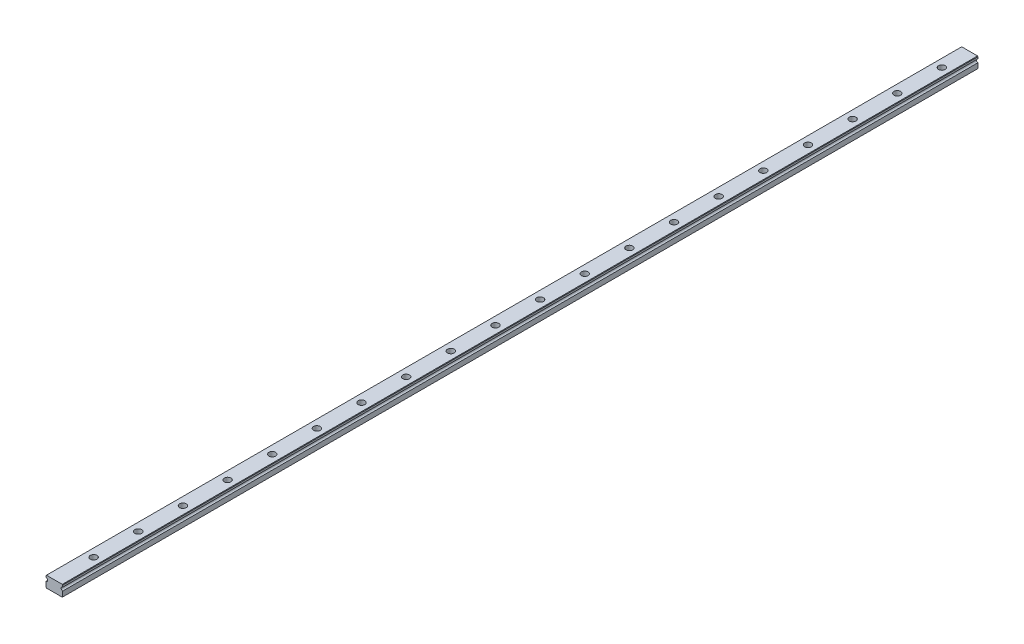
SolidWorks part; units mm, degrees
ref_plane "前视基准面" through (0, 0, 0) normal (0, 0, 1) x (1, 0, 0)
ref_plane "上视基准面" through (0, 0, 0) normal (0, 1, 0) x (1, 0, 0)
ref_plane "右视基准面" through (0, 0, 0) normal (1, 0, 0) x (0, 0, -1)
other "Configuration Table"
sketch "草图1" plane through (0, 0, 0) normal (0, 0, 1) x (1, 0, 0)
  line L0 (-7.6432, 0.2342) -> (-7.6432, -4.3658)
  line L1 (-7.6432, -4.3658) -> (-7.2432, -4.7658)
  line L2 (-7.2432, -4.7658) -> (6.9568, -4.7658)
  line L3 (6.9568, -4.7658) -> (7.3568, -4.3658)
  line L4 (7.3568, -4.3658) -> (7.3568, 0.2342)
  line L5 (7.3568, 3.2342) -> (7.3568, 4.8342)
  line L6 (7.3568, 4.8342) -> (6.9568, 5.2342)
  line L7 (6.9568, 5.2342) -> (-7.2432, 5.2342)
  line L8 (-7.2432, 5.2342) -> (-7.6432, 4.8342)
  line L9 (-7.6432, 4.8342) -> (-7.6432, 3.2342)
  arc A0 (5.8568, 1.7342) -> (7.3568, 0.2342) centre (7.3568, 1.7342) ccw
  arc A1 (7.3568, 3.2342) -> (5.8568, 1.7342) centre (7.3568, 1.7342) ccw
  arc A2 (-7.6432, 0.2342) -> (-7.6432, 3.2342) centre (-7.6432, 1.7342) ccw
extrude "凸台-拉伸1" add sketch "草图1" along normal blind 1000
sketch "草图2" plane through (0, 5.2342, 0) normal (0, 1, 0) x (1, 0, 0)
  circle A0 centre (0, -4.969) radius 1.5
  dimension "D1" = 3
extrude "切除-拉伸1" cut sketch "草图2" against normal blind 20
sketch "草图3" plane through (0, 5.2342, 0) normal (0, 1, 0) x (1, 0, 0)
  circle A0 centre (0, -4.969) radius 3
  dimension "D1" = 6
extrude "切除-拉伸2" cut sketch "草图3" against normal blind 4.5
sketch "草图4" plane through (0, 5.2342, 0) normal (0, 1, 0) x (1, 0, 0)
  line L0 (0, 0) -> (0, -1341.5051) construction
pattern_linear "阵列(线性)1" count 25 spacing 40 along (0, 0, 1) of "切除-拉伸2", "切除-拉伸1"
sketch "草图5" plane through (0, 0, 1000) normal (0, 0, 1) x (1, 0, 0)
  line L10 (-7.6432, 0.2342) -> (-7.6432, -4.3658)
  line L11 (-7.6432, -4.3658) -> (-7.2432, -4.7658)
  line L12 (-7.2432, -4.7658) -> (6.9568, -4.7658)
  line L13 (6.9568, -4.7658) -> (7.3568, -4.3658)
  line L14 (7.3568, -4.3658) -> (7.3568, 0.2342)
  line L15 (7.3568, 3.2342) -> (7.3568, 4.8342)
  line L16 (7.3568, 4.8342) -> (6.9568, 5.2342)
  line L17 (6.9568, 5.2342) -> (-7.2432, 5.2342)
  line L18 (-7.2432, 5.2342) -> (-7.6432, 4.8342)
  line L19 (-7.6432, 4.8342) -> (-7.6432, 3.2342)
  line L20 (-7.6432, 0.2342) -> (-7.6432, -4.3658)
  line L21 (-7.6432, -4.3658) -> (-7.2432, -4.7658)
  line L22 (-7.2432, -4.7658) -> (6.9568, -4.7658)
  line L23 (6.9568, -4.7658) -> (7.3568, -4.3658)
  line L24 (7.3568, -4.3658) -> (7.3568, 0.2342)
  line L25 (7.3568, 3.2342) -> (7.3568, 4.8342)
  line L26 (7.3568, 4.8342) -> (6.9568, 5.2342)
  line L27 (6.9568, 5.2342) -> (-7.2432, 5.2342)
  line L28 (-7.2432, 5.2342) -> (-7.6432, 4.8342)
  line L29 (-7.6432, 4.8342) -> (-7.6432, 3.2342)
  arc A2 (-7.6432, 0.2342) -> (-7.6432, 3.2342) centre (-7.6432, 1.7342) ccw
  arc A3 (7.3568, 3.2342) -> (7.3568, 0.2342) centre (7.3568, 1.7342) ccw
  arc A4 (-7.6432, 0.2342) -> (-7.6432, 3.2342) centre (-7.6432, 1.7342) ccw
  arc A5 (7.3568, 3.2342) -> (7.3568, 0.2342) centre (7.3568, 1.7342) ccw
  dimension "D1" = 0
sketch "草图6" plane through (0, 0, 0) normal (0, 0, -1) x (-1, 0, 0)
  line L10 (7.6432, 3.2342) -> (7.6432, 4.8342)
  line L11 (7.6432, 4.8342) -> (7.2432, 5.2342)
  line L12 (7.2432, 5.2342) -> (-6.9568, 5.2342)
  line L13 (-6.9568, 5.2342) -> (-7.3568, 4.8342)
  line L14 (-7.3568, 4.8342) -> (-7.3568, 3.2342)
  line L15 (-7.3568, 0.2342) -> (-7.3568, -4.3658)
  line L16 (-7.3568, -4.3658) -> (-6.9568, -4.7658)
  line L17 (-6.9568, -4.7658) -> (7.2432, -4.7658)
  line L18 (7.2432, -4.7658) -> (7.6432, -4.3658)
  line L19 (7.6432, -4.3658) -> (7.6432, 0.2342)
  line L20 (7.6432, 3.2342) -> (7.6432, 4.8342)
  line L21 (7.6432, 4.8342) -> (7.2432, 5.2342)
  line L22 (7.2432, 5.2342) -> (-6.9568, 5.2342)
  line L23 (-6.9568, 5.2342) -> (-7.3568, 4.8342)
  line L24 (-7.3568, 4.8342) -> (-7.3568, 3.2342)
  line L25 (-7.3568, 0.2342) -> (-7.3568, -4.3658)
  line L26 (-7.3568, -4.3658) -> (-6.9568, -4.7658)
  line L27 (-6.9568, -4.7658) -> (7.2432, -4.7658)
  line L28 (7.2432, -4.7658) -> (7.6432, -4.3658)
  line L29 (7.6432, -4.3658) -> (7.6432, 0.2342)
  arc A2 (7.6432, 3.2342) -> (7.6432, 0.2342) centre (7.6432, 1.7342) ccw
  arc A3 (-7.3568, 0.2342) -> (-7.3568, 3.2342) centre (-7.3568, 1.7342) ccw
  arc A4 (7.6432, 3.2342) -> (7.6432, 0.2342) centre (7.6432, 1.7342) ccw
  arc A5 (-7.3568, 0.2342) -> (-7.3568, 3.2342) centre (-7.3568, 1.7342) ccw
  dimension "D1" = 0
extrude "切除-拉伸4" cut sketch "草图6" against normal blind 80
sketch "草图7" plane through (0, 0, 80) normal (0, 0, -1) x (-1, 0, 0)
  line L10 (7.6432, 3.2342) -> (7.6432, 4.8342)
  line L11 (7.6432, 4.8342) -> (7.2432, 5.2342)
  line L12 (7.2432, 5.2342) -> (-6.9568, 5.2342)
  line L13 (-6.9568, 5.2342) -> (-7.3568, 4.8342)
  line L14 (-7.3568, 4.8342) -> (-7.3568, 3.2342)
  line L15 (-7.3568, 0.2342) -> (-7.3568, -4.3658)
  line L16 (-7.3568, -4.3658) -> (-6.9568, -4.7658)
  line L17 (-6.9568, -4.7658) -> (7.2432, -4.7658)
  line L18 (7.2432, -4.7658) -> (7.6432, -4.3658)
  line L19 (7.6432, -4.3658) -> (7.6432, 0.2342)
  line L20 (7.6432, 3.2342) -> (7.6432, 4.8342)
  line L21 (7.6432, 4.8342) -> (7.2432, 5.2342)
  line L22 (7.2432, 5.2342) -> (-6.9568, 5.2342)
  line L23 (-6.9568, 5.2342) -> (-7.3568, 4.8342)
  line L24 (-7.3568, 4.8342) -> (-7.3568, 3.2342)
  line L25 (-7.3568, 0.2342) -> (-7.3568, -4.3658)
  line L26 (-7.3568, -4.3658) -> (-6.9568, -4.7658)
  line L27 (-6.9568, -4.7658) -> (7.2432, -4.7658)
  line L28 (7.2432, -4.7658) -> (7.6432, -4.3658)
  line L29 (7.6432, -4.3658) -> (7.6432, 0.2342)
  arc A2 (7.6432, 3.2342) -> (7.6432, 0.2342) centre (7.6432, 1.7342) ccw
  arc A3 (-7.3568, 0.2342) -> (-7.3568, 3.2342) centre (-7.3568, 1.7342) ccw
  arc A4 (7.6432, 3.2342) -> (7.6432, 0.2342) centre (7.6432, 1.7342) ccw
  arc A5 (-7.3568, 0.2342) -> (-7.3568, 3.2342) centre (-7.3568, 1.7342) ccw
  dimension "D1" = 0
extrude "切除-拉伸5" cut sketch "草图7" against normal blind 80
sketch "草图8" plane through (0, 0, 160) normal (0, 0, -1) x (-1, 0, 0)
  line L10 (7.6432, 3.2342) -> (7.6432, 4.8342)
  line L11 (7.6432, 4.8342) -> (7.2432, 5.2342)
  line L12 (7.2432, 5.2342) -> (-6.9568, 5.2342)
  line L13 (-6.9568, 5.2342) -> (-7.3568, 4.8342)
  line L14 (-7.3568, 4.8342) -> (-7.3568, 3.2342)
  line L15 (-7.3568, 0.2342) -> (-7.3568, -4.3658)
  line L16 (-7.3568, -4.3658) -> (-6.9568, -4.7658)
  line L17 (-6.9568, -4.7658) -> (7.2432, -4.7658)
  line L18 (7.2432, -4.7658) -> (7.6432, -4.3658)
  line L19 (7.6432, -4.3658) -> (7.6432, 0.2342)
  line L20 (7.6432, 3.2342) -> (7.6432, 4.8342)
  line L21 (7.6432, 4.8342) -> (7.2432, 5.2342)
  line L22 (7.2432, 5.2342) -> (-6.9568, 5.2342)
  line L23 (-6.9568, 5.2342) -> (-7.3568, 4.8342)
  line L24 (-7.3568, 4.8342) -> (-7.3568, 3.2342)
  line L25 (-7.3568, 0.2342) -> (-7.3568, -4.3658)
  line L26 (-7.3568, -4.3658) -> (-6.9568, -4.7658)
  line L27 (-6.9568, -4.7658) -> (7.2432, -4.7658)
  line L28 (7.2432, -4.7658) -> (7.6432, -4.3658)
  line L29 (7.6432, -4.3658) -> (7.6432, 0.2342)
  arc A2 (7.6432, 3.2342) -> (7.6432, 0.2342) centre (7.6432, 1.7342) ccw
  arc A3 (-7.3568, 0.2342) -> (-7.3568, 3.2342) centre (-7.3568, 1.7342) ccw
  arc A4 (7.6432, 3.2342) -> (7.6432, 0.2342) centre (7.6432, 1.7342) ccw
  arc A5 (-7.3568, 0.2342) -> (-7.3568, 3.2342) centre (-7.3568, 1.7342) ccw
  dimension "D1" = 0
extrude "切除-拉伸6" cut sketch "草图8" against normal blind 20
